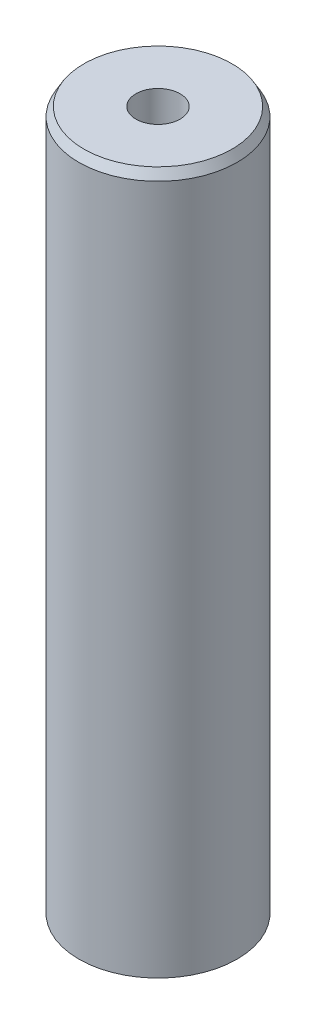
SolidWorks part; units mm, degrees
ref_plane "Front Plane" through (0, 0, 0) normal (0, 0, 1) x (1, 0, 0)
ref_plane "Top Plane" through (0, 0, 0) normal (0, 1, 0) x (1, 0, 0)
ref_plane "Right Plane" through (0, 0, 0) normal (1, 0, 0) x (0, 0, -1)
sketch "Sketch1" plane through (0, 0, 0) normal (0, 1, 0) x (1, 0, 0)
  circle A0 centre (0, 0) radius 12.5
  dimension "SHAFT_OD" = 25
extrude "Boss-Extrude1" add sketch "Sketch1" along normal blind 111.1643
sketch "Sketch2" plane through (0, 0, 0) normal (0, 1, 0) x (1, 0, 0)
  circle A0 centre (0, 0) radius 3.4851
  dimension "BORE_D" = 6.9702
extrude "Cut-Extrude1" cut sketch "Sketch2" along normal through all
chamfer "Chamfer1" distance 1.4049 angle 30 2 edges at (0, 111.1643, 12.5) (0, 0, 12.5) first distance on face at (0, 111.1643, 12.5) first distance on face at (0, 0, 3.4851)
